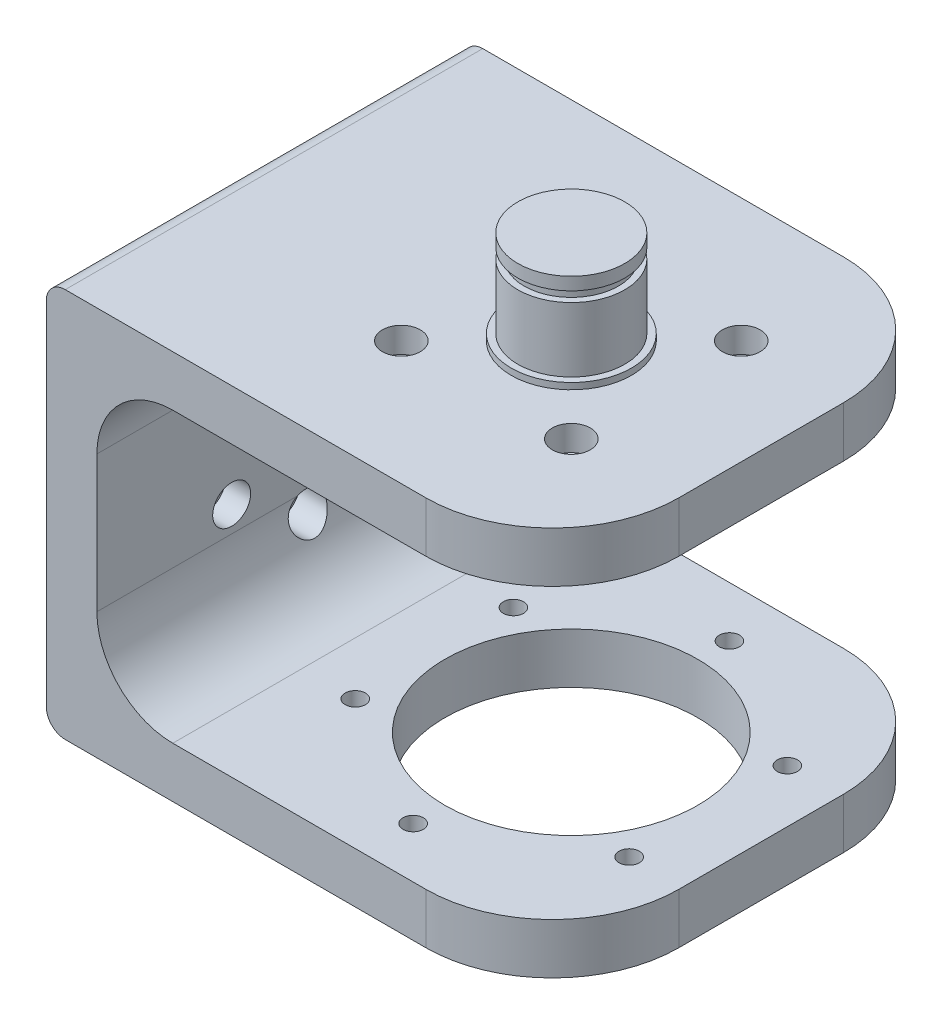
SolidWorks part; units mm, degrees
material "PETG-CF"
ref_plane "Front Plane" through (0, 0, 0) normal (0, 0, 1) x (1, 0, 0)
ref_plane "Top Plane" through (0, 0, 0) normal (0, 1, 0) x (1, 0, 0)
ref_plane "Right Plane" through (0, 0, 0) normal (1, 0, 0) x (0, 0, -1)
sketch "草图1" plane through (0, 0, 0) normal (0, 1, 0) x (1, 0, 0)
  line L1 (40, -33) -> (-40, -33)
  line L2 (40, -33) -> (40, 33)
  line L3 (40, 33) -> (-40, 33)
  line L4 (-40, -33) -> (-40, 33)
  line L5 (40, -33) -> (-40, 33) construction
  line L6 (40, 33) -> (-40, -33) construction
  point P0 (0, 0)
  dimension "D1" = 66
  dimension "D2" = 80
extrude "凸台-拉伸1" add sketch "草图1" along normal blind 8
sketch "草图2" plane through (0, 8, 0) normal (0, 1, 0) x (1, 0, 0)
  line L0 (-40, -33) -> (40, -33) construction
  line L1 (-32, -33) -> (-40, -33)
  line L2 (-32, -33) -> (-32, 33)
  line L3 (-32, 33) -> (-40, 33)
  line L4 (-40, -33) -> (-40, 33)
  line L5 (-32, -33) -> (-40, 33) construction
  line L6 (-32, 33) -> (-40, -33) construction
  point P0 (-36, 0)
  dimension "D1" = 8
extrude "凸台-拉伸2" add sketch "草图2" along normal blind 53.6
sketch "草图5" plane through (-32, 0, 0) normal (1, 0, 0) x (0, 0, -1)
  line L0 (-33, 61.6) -> (-33, 8) construction
  line L1 (33, 53.6) -> (-33, 53.6)
  line L2 (33, 53.6) -> (33, 61.6)
  line L3 (33, 61.6) -> (-33, 61.6)
  line L4 (-33, 53.6) -> (-33, 61.6)
  line L5 (33, 53.6) -> (-33, 61.6) construction
  line L6 (33, 61.6) -> (-33, 53.6) construction
  line L7 (33, 61.6) -> (33, 8) construction
  line L9 (-33, 61.6) -> (33, 61.6) construction
  point P0 (0, 57.6)
  dimension "D1" = 8
extrude "凸台-拉伸3" add sketch "草图5" along normal through all
sketch "草图4" plane through (0, 8, 0) normal (0, 1, 0) x (1, 0, 0)
  line L0 (-40, 33) -> (-40, -33) construction
  line L2 (40, -33) -> (40, 33) construction
  circle A0 centre (10, 0) radius 25 construction
  circle A1 centre (10, 25) radius 1.6
  circle A2 centre (-11.6506, 12.5) radius 1.6
  circle A3 centre (-11.6506, -12.5) radius 1.6
  circle A4 centre (10, -25) radius 1.6
  circle A5 centre (10, 0) radius 20
  circle A6 centre (31.6506, -12.5) radius 1.6
  circle A7 centre (31.6506, 12.5) radius 1.6
  point P17 (10, 0)
  point P22 (-40, 0)
  dimension "D3" = 50
  dimension "D4" = 3.2
  dimension "D6" = 40
  dimension "D1" = 30
  dimension "D5" = 6
extrude "切除-拉伸1" cut sketch "草图4" against normal through all contours A5 | A2 | A1 | A4 | A3 | A7 | A6
sketch "草图7" plane through (0, 61.6, 0) normal (0, 1, 0) x (1, 0, 0)
  line L0 (40, 33) -> (40, -33) construction
  line L2 (40, 33) -> (40, -33) construction
  line L3 (10, 0) -> (-3.435, 13.435) construction
  line L4 (10, 0) -> (10, 19) construction
  circle A0 centre (10, 0) radius 19 construction
  circle A5 centre (-3.435, 13.435) radius 1.6
  circle A6 centre (23.435, 13.435) radius 1.6
  circle A7 centre (23.435, -13.435) radius 1.6
  circle A8 centre (-3.435, -13.435) radius 1.6
  point P10 (40, 0)
  point P18 (10, 0)
  point P20 (10, 0)
  dimension "D1" = 38
  dimension "D4" = 45
  dimension "D5" = 3.2
  dimension "D3" = 30
  dimension "D6" = 4
extrude "切除-拉伸3" cut sketch "草图7" against normal up to next
fillet "圆角3" radius 20 4 edges at (40, 4, 33) (40, 4, -33) (40, 57.6, -33) (40, 57.6, 33)
fillet "圆角5" radius 3 2 edges at (-40, 0, 0) (-40, 61.6, 0)
sketch "草图8" plane through (0, 61.6, 0) normal (0, 1, 0) x (1, 0, 0)
  circle A0 centre (10, 0) radius 8.45
  dimension "D1" = 16.9
extrude "凸台-拉伸4" add sketch "草图8" along normal blind 14.8
ref_plane "基准面1" through (0, 74.4, 0) normal (0, 1, 0) x (1, 0, 0)
sketch "草图10" plane through (0, 74.4, 0) normal (0, 1, 0) x (1, 0, 0)
  circle A0 centre (10, 0) radius 8.45
  circle A1 centre (10, 0) radius 7.45
  dimension "D1" = 14.9
extrude "切除-拉伸4" cut sketch "草图10" against normal blind 1.6
ref_plane "基准面2" through (-36, 0, 0) normal (-1, 0, 0) x (0, 0, 1)
sketch "草图14" plane through (0, 61.6, 0) normal (0, 1, 0) x (1, 0, 0)
  circle A0 centre (-3.435, 13.435) radius 3
  circle A1 centre (23.435, 13.435) radius 3
  circle A2 centre (23.435, -13.435) radius 3
  circle A3 centre (-3.435, -13.435) radius 3
  point P12 (10, 0)
  dimension "D1" = 6
  dimension "D2" = 4
extrude "切除-拉伸6" cut sketch "草图14" against normal blind 4
sketch "草图15" plane through (0, 0, 0) normal (0, -1, 0) x (1, 0, 0)
  circle A0 centre (-11.6506, 12.5) radius 3
  circle A1 centre (10, 25) radius 3
  circle A2 centre (31.6506, 12.5) radius 3
  circle A3 centre (31.6506, -12.5) radius 3
  circle A4 centre (10, -25) radius 3
  circle A5 centre (-11.6506, -12.5) radius 3
  point P15 (10, 0)
  dimension "D1" = 6
  dimension "D2" = 6
extrude "切除-拉伸7" cut sketch "草图15" against normal blind 4
sketch "草图16" plane through (0, 61.6, 0) normal (0, 1, 0) x (1, 0, 0)
  circle A0 centre (10, 0) radius 9.5
  dimension "D1" = 19
extrude "凸台-拉伸5" add sketch "草图16" along normal blind 1
sketch "Sketch1" plane through (-40, 0, 0) normal (-1, 0, 0) x (0, 0, 1)
  line L0 (33, 58.6) -> (33, 3) construction
  circle A0 centre (0, 30.8) radius 18
  point P2 (0, 0)
  point P4 (0, 0)
  point P5 (0, 0)
  point P8 (33, 30.8)
  dimension "D1" = 36
extrude "Boss-Extrude1" add sketch "Sketch1" along normal blind 9.8
sketch "Sketch2" plane through (-49.8, 0, 0) normal (-1, 0, 0) x (0, 0, 1)
  circle A0 centre (0, 30.8) radius 13.5 construction
  circle A1 centre (0, 30.8) radius 4
  circle A2 centre (0, 17.3) radius 1.6
  circle A3 centre (-11.6913, 24.05) radius 1.6
  circle A4 centre (-11.6913, 37.55) radius 1.6
  circle A5 centre (0, 44.3) radius 1.6
  circle A6 centre (11.6913, 37.55) radius 1.6
  circle A7 centre (11.6913, 24.05) radius 1.6
  point P7 (0, 30.8)
  point P8 (0, 30.8)
  point P18 (0, 30.8)
  dimension "D1" = 27
  dimension "D2" = 8
  dimension "D3" = 3.2
  dimension "D4" = 6
extrude "Cut-Extrude1" cut sketch "Sketch2" against normal through all
sketch "Sketch4" plane through (-32, 0, 0) normal (1, 0, 0) x (0, 0, -1)
  circle A0 centre (0, 44.3) radius 3
  circle A1 centre (11.6913, 37.55) radius 3
  circle A2 centre (11.6913, 24.05) radius 3
  circle A3 centre (0, 17.3) radius 3
  circle A4 centre (-11.6913, 24.05) radius 3
  circle A5 centre (-11.6913, 37.55) radius 3
  point P4 (0, 30.8)
  point P15 (0, 30.8)
  dimension "D1" = 6
  dimension "D2" = 6
extrude "Cut-Extrude2" cut sketch "Sketch4" against normal blind 4
fillet "圆角4" radius 12 2 edges at (-32, 8, 0) (-32, 53.6, 0)
